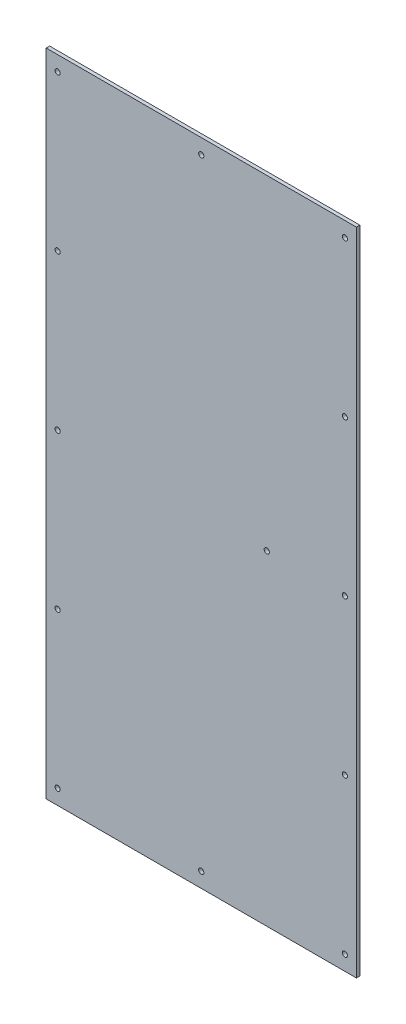
SolidWorks part; units mm, degrees
ref_plane "Спереди" through (0, 0, 0) normal (0, 0, 1) x (1, 0, 0)
ref_plane "Сверху" through (0, 0, 0) normal (0, 1, 0) x (1, 0, 0)
ref_plane "Справа" through (0, 0, 0) normal (1, 0, 0) x (0, 0, -1)
sketch "Эскиз1" plane through (0, 0, 0) normal (0, 0, 1) x (1, 0, 0)
  line L0 (0, 0) -> (270, 0)
  line L1 (0, 0) -> (0, 566)
  line L2 (270, 0) -> (270, 566)
  line L3 (0, 566) -> (270, 566)
  line L4 (10, 553) -> (260, 553) construction
  line L5 (10, 553) -> (10, 13) construction
  line L6 (260, 553) -> (260, 13) construction
  line L7 (10, 13) -> (260, 13) construction
  line L8 (135, 553) -> (135, 13) construction
  circle A0 centre (10, 553) radius 2.25
  circle A1 centre (10, 418) radius 2.25
  circle A2 centre (10, 283) radius 2.25
  circle A3 centre (10, 148) radius 2.25
  circle A4 centre (10, 13) radius 2.25
  circle A5 centre (135, 553) radius 2.25
  circle A6 centre (135, 13) radius 2.25
  circle A7 centre (260, 553) radius 2.25
  circle A8 centre (260, 418) radius 2.25
  circle A9 centre (260, 283) radius 2.25
  circle A10 centre (260, 148) radius 2.25
  circle A11 centre (260, 13) radius 2.25
  dimension "D7" = 4.5
  dimension "D9" = 135
  dimension "D10" = 4.5
  dimension "D12" = 135
  dimension "D13" = 4.5
  dimension "D22" = 4.5
  dimension "D1" = 566
  dimension "D2" = 270
  dimension "D3" = 10
  dimension "D4" = 13
  dimension "D5" = 10
  dimension "D6" = 13
  dimension "D8" = 5
  dimension "D11" = 5
extrude "Бобышка-Вытянуть1" add sketch "Эскиз1" along normal blind 3
sketch "Sketch1" plane through (0, 0, 3) normal (0, 0, 1) x (1, 0, 0)
  line L0 (182, 543) -> (182, 23) construction
  line L1 (182, 543) -> (182, 23) construction
  line L2 (202, 543) -> (202, 23) construction
  line L3 (202, 543) -> (202, 23) construction
  line L4 (202, 283) -> (182, 283) construction
  circle A0 centre (192, 283) radius 2.25
  dimension "D1" = 4.5
  dimension "D2" = 10
extrude "Cut-Extrude1" cut sketch "Sketch1" against normal through all
